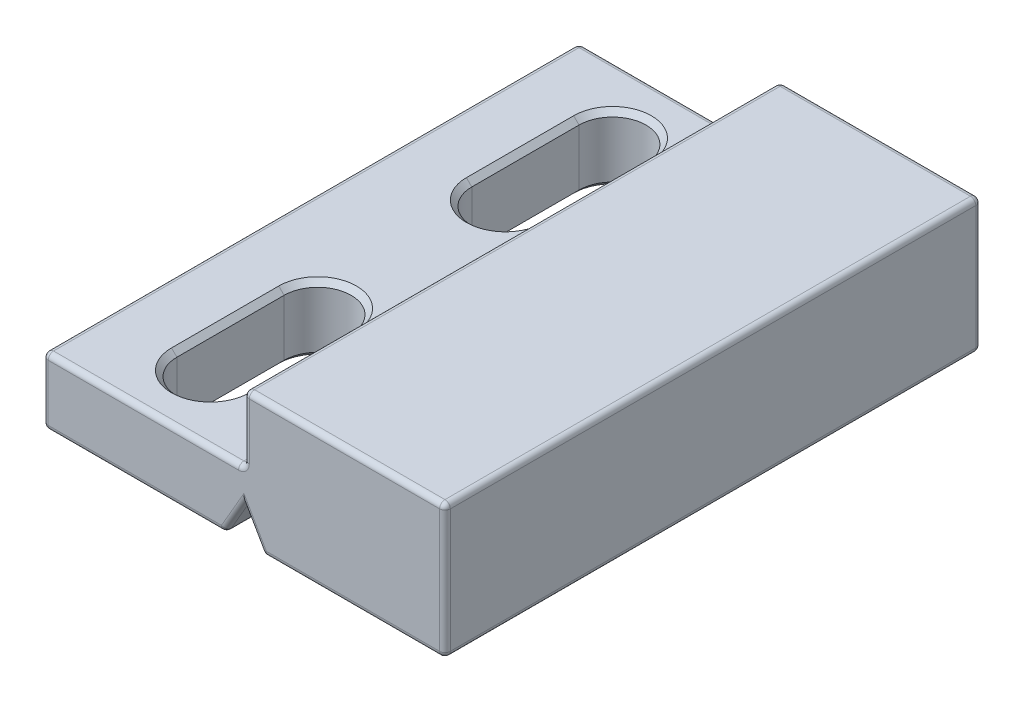
SolidWorks part; units mm, degrees
ref_plane "Front (1)" through (0, 0, 0) normal (0, 0, 1) x (1, 0, 0)
ref_plane "Top (2)" through (0, 0, 0) normal (0, 1, 0) x (1, 0, 0)
ref_plane "Right (3)" through (0, 0, 0) normal (1, 0, 0) x (0, 0, -1)
ref_axis "X-Axis" through (-80.9, 0, 0) along (1, 0, 0)
ref_axis "Y-Axis" through (0, -50, 0) along (0, 1, 0)
ref_axis "Z-Axis" through (0, 0, 50) along (0, 0, -1)
sketch "Sketch1" plane through (0, 0, 0) normal (0, 1, 0) x (1, 0, 0)
  line L1 (0, 0) -> (19.05, 0)
  line L2 (0, 0) -> (0, 25.4)
  line L3 (0, 25.4) -> (19.05, 25.4)
  line L4 (19.05, 0) -> (19.05, 25.4)
  dimension "D1" = 19.05
  dimension "D2" = 25.4
extrude "Boss-Extrude1" add sketch "Sketch1" along normal blind 6.35
sketch "Sketch2" plane through (0, 6.35, 0) normal (0, 1, 0) x (1, 0, 0)
  line L0 (19.05, 25.4) -> (0, 25.4) construction
  line L1 (0, 0) -> (9.525, 0)
  line L2 (0, 0) -> (0, 25.4)
  line L3 (0, 25.4) -> (9.525, 25.4)
  line L4 (9.525, 0) -> (9.525, 25.4)
extrude "Cut-Extrude1" cut sketch "Sketch2" against normal blind 3.175
sketch "Sketch3" plane through (0, 0, 0) normal (0, 0, 1) x (1, 0, 0)
  line L0 (8.6085, 0) -> (9.525, 1.5875)
  line L1 (0, 0) -> (19.05, 0) construction
  line L2 (9.525, 1.5875) -> (10.4415, 0)
  line L3 (10.4415, 0) -> (8.6085, 0)
  line L4 (9.525, 3.175) -> (9.525, 6.35) construction
  dimension "D1" = 60
  dimension "D2" = 1.5875
extrude "Cut-Extrude2" cut sketch "Sketch3" against normal through all
sketch "Sketch4" plane through (0, 3.175, 0) normal (0, 1, 0) x (1, 0, 0)
  line L0 (4.7625, 22.225) -> (4.7625, 17.145) construction
  line L1 (6.35, 22.225) -> (6.35, 17.145)
  line L2 (3.175, 22.225) -> (3.175, 17.145)
  line L3 (4.7625, 8.255) -> (4.7625, 3.175) construction
  line L4 (6.35, 8.255) -> (6.35, 3.175)
  line L5 (3.175, 8.255) -> (3.175, 3.175)
  line L6 (0, 0) -> (9.525, 0) construction
  line L7 (9.525, 25.4) -> (0, 25.4) construction
  arc A0 (6.35, 22.225) -> (3.175, 22.225) centre (4.7625, 22.225) ccw
  arc A1 (3.175, 17.145) -> (6.35, 17.145) centre (4.7625, 17.145) ccw
  arc A2 (6.35, 8.255) -> (3.175, 8.255) centre (4.7625, 8.255) ccw
  arc A3 (3.175, 3.175) -> (6.35, 3.175) centre (4.7625, 3.175) ccw
  point P2 (4.7625, 19.685)
  point P7 (4.7625, 5.715)
  point P16 (4.7625, 0)
  dimension "D1" = 3.175
  dimension "D2" = 5.08
  dimension "D3" = 5.08
  dimension "D4" = 3.175
  dimension "D5" = 3.175
  dimension "D6" = 3.175
extrude "Cut-Extrude3" cut sketch "Sketch4" against normal through all
fillet "Fillet1" radius 0.254 26 edges at (19.05, 0, -12.7) (10.4415, 0, -12.7) (14.7458, 0, -25.4) (19.05, 3.175, -25.4) (9.525, 4.7625, -25.4) (4.7625, 3.175, -25.4) (0, 1.5875, -25.4) (4.3042, 0, -25.4) (9.0667, 0.7937, -25.4) (9.9833, 0.7937, -25.4) (0, 1.5875, 0) (4.7625, 3.175, 0) (9.525, 4.7625, 0) (19.05, 3.175, 0) (14.7458, 0, 0) (9.9833, 0.7937, 0) (9.0667, 0.7937, 0) (4.3042, 0, 0) (19.05, 6.35, -12.7) (14.2875, 6.35, 0) (9.525, 6.35, -12.7) (14.2875, 6.35, -25.4) (0, 3.175, -12.7) (0, 0, -12.7) (8.6085, 0, -12.7) (9.525, 3.175, -12.7)
chamfer "Chamfer1" distance 0.254 angle 45 16 edges at (3.175, 0, -19.685) (4.7625, 0, -15.5575) (4.7625, 0, -23.8125) (6.35, 0, -19.685) (3.175, 3.175, -19.685) (4.7625, 3.175, -15.5575) (4.7625, 3.175, -23.8125) (6.35, 3.175, -19.685) (3.175, 0, -5.715) (4.7625, 0, -1.5875) (4.7625, 0, -9.8425) (6.35, 0, -5.715) (3.175, 3.175, -5.715) (4.7625, 3.175, -1.5875) (4.7625, 3.175, -9.8425) (6.35, 3.175, -5.715)
